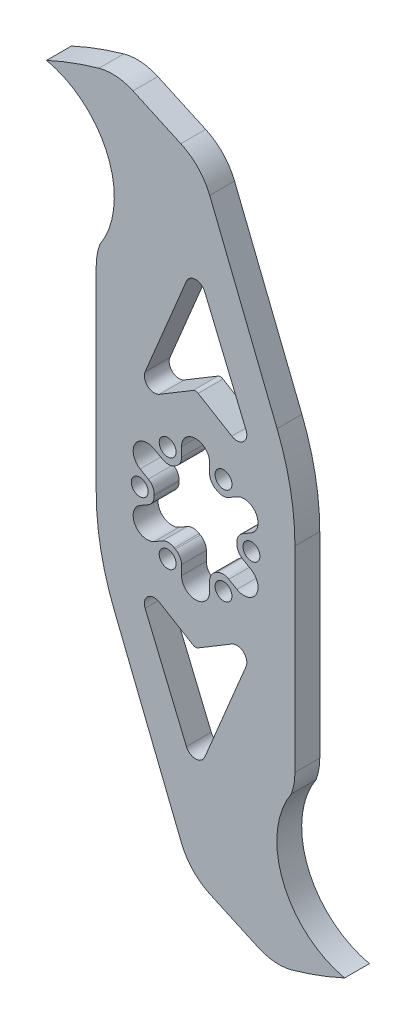
SolidWorks part; units mm, degrees
material "AISI Type A2 Tool Steel"
ref_plane "Front Plane" through (0, 0, 0) normal (0, 0, 1) x (1, 0, 0)
ref_plane "Top Plane" through (0, 0, 0) normal (0, 1, 0) x (1, 0, 0)
ref_plane "Right Plane" through (0, 0, 0) normal (1, 0, 0) x (0, 0, -1)
sketch "Model" plane through (0, 0, 0) normal (0, 0, 1) x (1, 0, 0)
  line L0 (-12.0864, 2.8334) -> (-14.1681, 4.0352)
  line L1 (-10.5786, 10.2523) -> (-8.497, 9.0505)
  line L2 (-3.5895, 11.8838) -> (-3.5895, 14.2875)
  line L3 (3.5895, 14.2875) -> (3.5895, 11.8838)
  line L4 (8.497, 9.0505) -> (10.5786, 10.2523)
  line L5 (14.1681, 4.0352) -> (12.0864, 2.8334)
  line L6 (12.0864, -2.8334) -> (14.1681, -4.0352)
  line L7 (10.5786, -10.2523) -> (8.497, -9.0505)
  line L8 (3.5895, -11.8838) -> (3.5895, -14.2875)
  line L9 (-3.5895, -14.2875) -> (-3.5895, -11.8838)
  line L10 (-8.497, -9.0505) -> (-10.5786, -10.2523)
  line L11 (-14.1681, -4.0352) -> (-12.0864, -2.8334)
  line L12 (20.8343, 30.4641) -> (3.6175, 73.5062)
  line L13 (-9.7405, 82.55) -> (-38.1, 82.55)
  line L14 (-38.1, 82.55) -> (-31.75, 57.15)
  line L15 (-25.4, 46.0553) -> (-25.4, -6.7566)
  line L16 (-20.8343, -30.4641) -> (-3.6175, -73.5062)
  line L17 (9.7405, -82.55) -> (38.1, -82.55)
  line L18 (38.1, -82.55) -> (31.75, -57.15)
  line L19 (25.4, -46.0553) -> (25.4, 6.7566)
  circle A0 centre (7.1437, -12.3733) radius 2.159
  circle A1 centre (-7.1437, 12.3733) radius 2.159
  circle A2 centre (14.2875, 0) radius 2.159
  circle A3 centre (-7.1438, -12.3733) radius 2.159
  circle A4 centre (7.1438, 12.3733) radius 2.159
  circle A5 centre (-14.2875, 0) radius 2.159
  arc A6 (-10.5786, 10.2523) -> (-14.1681, 4.0352) centre (-12.3733, 7.1438) ccw
  arc A7 (-8.497, 9.0505) -> (-5.4291, 9.0744) centre (-6.9834, 11.6721) ccw
  arc A8 (-5.1441, 9.2389) -> (-5.4291, 9.0744) centre (0, 0) ccw
  arc A9 (-5.1441, 9.2389) -> (-3.5895, 11.8838) centre (-6.6167, 11.8838) ccw
  arc A10 (3.5895, 14.2875) -> (-3.5895, 14.2875) centre (0, 14.2875) ccw
  arc A11 (3.5895, 11.8838) -> (5.1441, 9.2389) centre (6.6167, 11.8838) ccw
  arc A12 (5.4291, 9.0744) -> (5.1441, 9.2389) centre (0, 0) ccw
  arc A13 (5.4291, 9.0744) -> (8.497, 9.0505) centre (6.9834, 11.6721) ccw
  arc A14 (14.1681, 4.0352) -> (10.5786, 10.2523) centre (12.3733, 7.1437) ccw
  arc A15 (12.0864, 2.8334) -> (10.5732, 0.1646) centre (13.6001, 0.2117) ccw
  arc A16 (10.5732, -0.1646) -> (10.5732, 0.1646) centre (0, 0) ccw
  arc A17 (10.5732, -0.1646) -> (12.0864, -2.8334) centre (13.6001, -0.2117) ccw
  arc A18 (10.5786, -10.2523) -> (14.1681, -4.0352) centre (12.3733, -7.1438) ccw
  arc A19 (8.497, -9.0505) -> (5.4291, -9.0744) centre (6.9834, -11.6721) ccw
  arc A20 (5.1441, -9.2389) -> (5.4291, -9.0744) centre (0, 0) ccw
  arc A21 (5.1441, -9.2389) -> (3.5895, -11.8838) centre (6.6167, -11.8838) ccw
  arc A22 (-3.5895, -14.2875) -> (3.5895, -14.2875) centre (0, -14.2875) ccw
  arc A23 (-3.5895, -11.8838) -> (-5.1441, -9.2389) centre (-6.6167, -11.8838) ccw
  arc A24 (-5.4291, -9.0744) -> (-5.1441, -9.2389) centre (0, 0) ccw
  arc A25 (-5.4291, -9.0744) -> (-8.497, -9.0505) centre (-6.9834, -11.6721) ccw
  arc A26 (-14.1681, -4.0352) -> (-10.5786, -10.2523) centre (-12.3733, -7.1437) ccw
  arc A27 (-12.0864, -2.8334) -> (-10.5732, -0.1646) centre (-13.6001, -0.2117) ccw
  arc A28 (-10.5732, 0.1646) -> (-10.5732, -0.1646) centre (0, 0) ccw
  arc A29 (-10.5732, 0.1646) -> (-12.0864, 2.8334) centre (-13.6001, 0.2117) ccw
  arc A30 (25.4, 6.7566) -> (20.8343, 30.4641) centre (-38.4345, 6.7566) ccw
  arc A31 (3.6175, 73.5062) -> (-9.7405, 82.55) centre (-9.7405, 68.1629) ccw
  arc A32 (-25.4, 46.0553) -> (-31.75, 57.15) centre (-38.2674, 46.0553) ccw
  arc A33 (-25.4, -6.7566) -> (-20.8343, -30.4641) centre (38.4345, -6.7566) ccw
  arc A34 (-3.6175, -73.5062) -> (9.7405, -82.55) centre (9.7405, -68.1629) ccw
  arc A35 (25.4, -46.0553) -> (31.75, -57.15) centre (38.2674, -46.0553) ccw
extrude "Boss-Extrude1" add sketch "Model" along normal mid plane 6.35
sketch "Sketch2" plane through (0, 0, 3.175) normal (0, 0, 1) x (1, 0, 0)
  circle A0 centre (0, 0) radius 4.826
  dimension "D1" = 9.652
sketch "Sketch3" plane through (0, 0, 3.175) normal (0, 0, 1) x (1, 0, 0)
  line L0 (0, 0) -> (38.1, -82.55) construction
  line L1 (0, 0) -> (-38.1, 82.55) construction
  line L2 (38.1, -82.55) -> (22.0448, -55.3402)
  line L3 (25.4, -46.0553) -> (22.0448, -55.3402)
  line L4 (31.75, -57.15) -> (25.4, -46.0553)
  line L5 (22.0448, -55.3402) -> (28.575, -51.6026) construction
  line L6 (38.1, -82.55) -> (31.75, -57.15)
  line L7 (-37.6802, -17.3909) -> (37.6802, 17.3909)
  line L8 (-38.1, 82.55) -> (-31.75, 57.15)
  line L9 (-31.75, 57.15) -> (-25.4, 46.0553)
  line L11 (-25.4, 46.0553) -> (-22.0448, 55.3402)
  line L12 (-22.0448, 55.3402) -> (-38.1, 82.55)
  point P16 (0, 0)
  dimension "D1" = 3.175
extrude "Cut-Extrude1" cut sketch "Sketch3" against normal through all contours L11 L12 L8 L9 | L2 L6 L4 L3 region at (29.4022, -61.4806, 3.175) region at (-29.4022, 61.4806, 3.175)
sketch "Sketch4" plane through (0, 0, 3.175) normal (0, 0, 1) x (1, 0, 0)
  line L0 (38.1, -82.55) -> (0, 0) construction
  line L1 (0, 0) -> (-38.1, 82.55) construction
  line L2 (-9.7405, 82.55) -> (-38.1, 82.55) construction
  circle A0 centre (0, 0) radius 90.9182 construction
fillet "Fillet1" radius 15.24 4 edges at (-22.0448, 55.3402, 0) (22.0448, -55.3402, 0) (25.4, -46.0553, 0) (-25.4, 46.0553, 0)
sketch "Sketch5" plane through (0, 0, 3.175) normal (0, 0, 1) x (1, 0, 0)
  line L0 (20.0622, -88.6771) -> (3.7746, -81.2547)
  line L1 (3.7746, -81.2547) -> (38.1, -82.55)
  line L4 (-20.0622, 88.6771) -> (-3.7746, 81.2547)
  line L5 (-3.7746, 81.2547) -> (-38.1, 82.55)
  arc A0 (38.1, -82.55) -> (20.0622, -88.6771) centre (0, 0) cw
  arc A1 (-3.6175, -73.5062) -> (9.7405, -82.55) centre (9.7405, -68.1629) ccw construction
  arc A4 (3.6175, 73.5062) -> (-9.7405, 82.55) centre (-9.7405, 68.1629) ccw construction
  arc A9 (-38.1, 82.55) -> (-20.0622, 88.6771) centre (0, 0) cw
  dimension "D1" = 19.05
  dimension "D2" = 19.05
extrude "Boss-Extrude2" add sketch "Sketch5" against normal up to surface (6.35 mm away) up to face at (0, 0, -3.175)
sketch "Sketch6" plane through (0, 0, 3.175) normal (0, 0, 1) x (1, 0, 0)
  line L1 (24.4929, -48.5655) -> (38.1, -82.55)
  arc A0 (38.1, -82.55) -> (24.4929, -48.5655) centre (42.9998, -60.8718) cw
  dimension "D1" = 22.225
extrude "Cut-Extrude2" cut sketch "Sketch6" against normal up to surface (6.35 mm away) up to face at (0, 0, -3.175)
sketch "Sketch7" plane through (0, 0, 3.175) normal (0, 0, 1) x (1, 0, 0)
  line L1 (-24.4826, 48.594) -> (-38.1, 82.55)
  arc A0 (-38.1, 82.55) -> (-24.4826, 48.594) centre (-43.0073, 60.8735) cw
  dimension "D1" = 22.225
extrude "Cut-Extrude3" cut sketch "Sketch7" against normal up to surface (6.35 mm away) up to face at (0, 0, -3.175)
fillet "Fillet2" radius 12.7 2 edges at (20.0622, -88.6771, 0) (-20.0622, 88.6771, 0)
sketch "Sketch8" plane through (0, 0, 3.175) normal (0, 0, 1) x (1, 0, 0)
  line L0 (0, 28.575) -> (-15.875, 19.05)
  line L1 (-15.875, 19.05) -> (0, 57.15)
  line L3 (-25.4, 43.3861) -> (-25.4, -6.7566) construction
  line L4 (0, 90.9182) -> (0, 57.15) construction
  line L5 (15.875, 19.05) -> (0, 57.15)
  line L6 (0, 28.575) -> (15.875, 19.05)
  line L7 (25.4, 0) -> (-25.4, 0) construction
  line L10 (0, -28.575) -> (15.875, -19.05)
  line L11 (15.875, -19.05) -> (0, -57.15)
  line L12 (-15.875, -19.05) -> (0, -57.15)
  line L13 (0, -28.575) -> (-15.875, -19.05)
  line L14 (0, 28.575) -> (0, -28.575) construction
  line L15 (0, -57.15) -> (0, -90.9182) construction
  circle A0 centre (0, 0) radius 90.9182 construction
  point P14 (0, 0)
  dimension "D1" = 9.525
  dimension "D2" = 9.525
  dimension "D3" = 28.575
  dimension "D4" = 38.1
extrude "Cut-Extrude4" cut sketch "Sketch8" against normal up to surface (6.35 mm away) up to face at (0, 0, -3.175)
fillet "Fillet3" radius 2.54 6 edges at (0, 57.15, 0) (-15.875, 19.05, 0) (15.875, 19.05, 0) (0, -57.15, 0) (15.875, -19.05, 0) (-15.875, -19.05, 0)
fillet "Fillet4" radius 1.27 2 edges at (0, 28.575, 0) (0, -28.575, 0)
